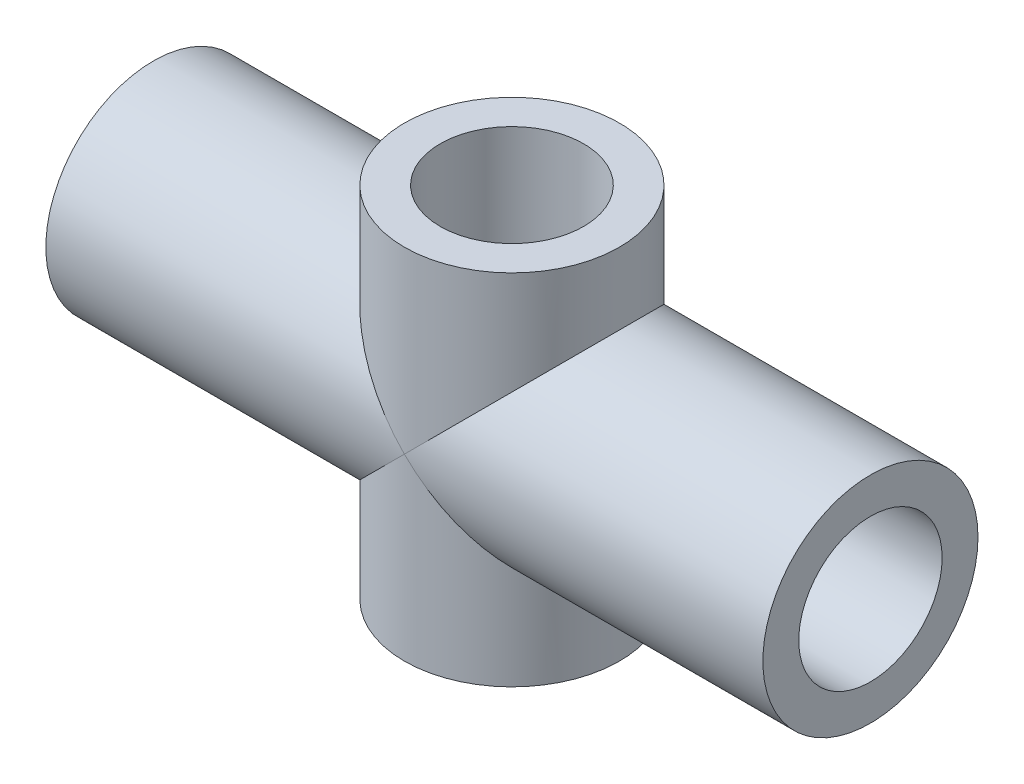
SolidWorks part; units mm, degrees
material "LWPLA"
ref_plane "Front Plane" through (0, 0, 0) normal (0, 0, 1) x (1, 0, 0)
ref_plane "Top Plane" through (0, 0, 0) normal (0, 1, 0) x (1, 0, 0)
ref_plane "Right Plane" through (0, 0, 0) normal (1, 0, 0) x (0, 0, -1)
sketch "Sketch1" plane through (0, 0, 0) normal (0, 1, 0) x (1, 0, 0)
  circle A1 centre (0, 0) radius 3
  dimension "D2" = 6
extrude "Boss-Extrude1" add sketch "Sketch1" along normal blind 5 and the other way blind 5
sketch "Sketch2" plane through (0, 0, 0) normal (1, 0, 0) x (0, 0, -1)
  circle A0 centre (0, 0) radius 3
  dimension "D1" = 6
extrude "Boss-Extrude3" add sketch "Sketch2" along normal blind 10 and the other way blind 10 contours A0
shell "Shell2" thickness 1 removed face at (0, -5, 3) removed face at (-10, 0, -3) removed face at (10, 0, -3) removed face at (0, 5, 3)
